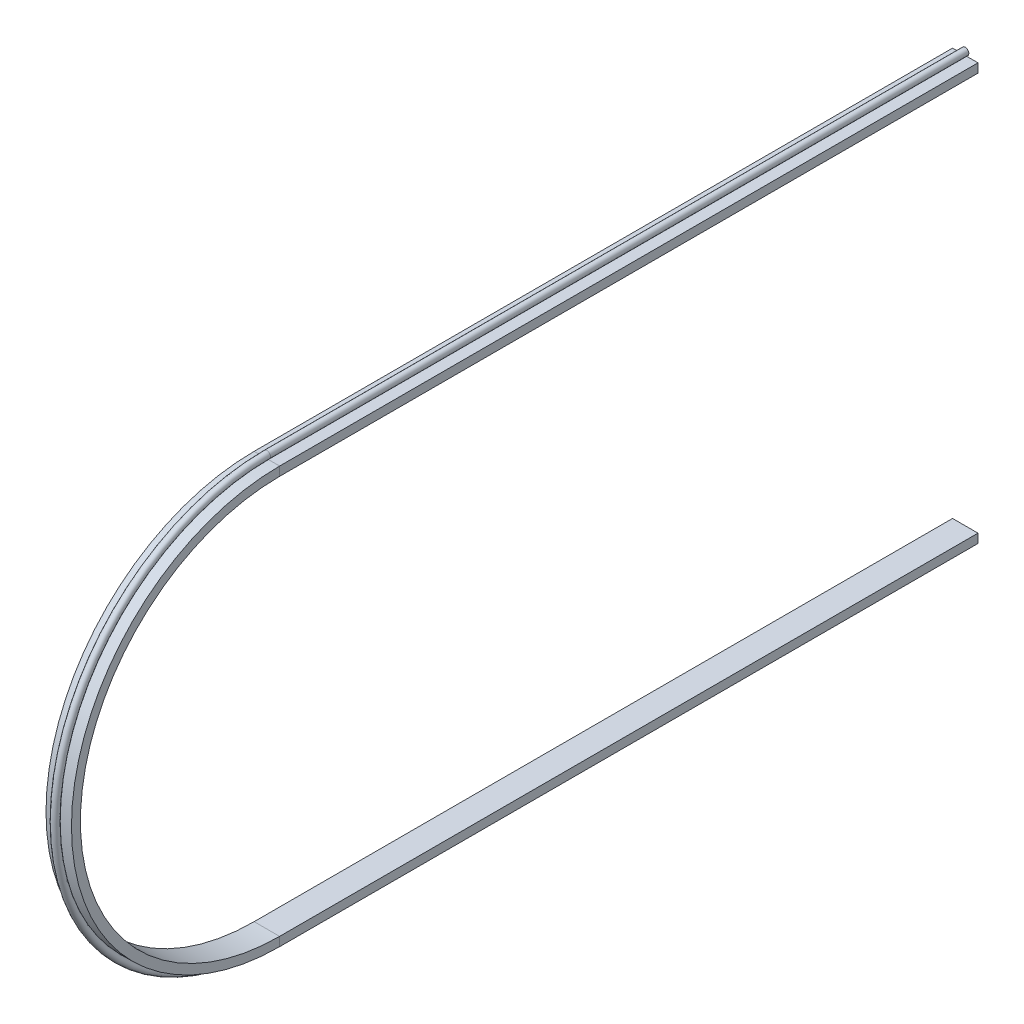
SolidWorks part; units mm, degrees
ref_plane "Front Plane" through (0, 0, 0) normal (0, 0, 1) x (1, 0, 0)
ref_plane "Top Plane" through (0, 0, 0) normal (0, 1, 0) x (1, 0, 0)
ref_plane "Right Plane" through (0, 0, 0) normal (1, 0, 0) x (0, 0, -1)
sketch "Sketch1" plane through (0, 0, 0) normal (0, 0, 1) x (1, 0, 0)
  line L1 (-6.25, -2.2) -> (6.25, -2.2)
  line L2 (-6.25, -2.2) -> (-6.25, 2.2)
  line L3 (-6.25, 2.2) -> (6.25, 2.2)
  line L4 (6.25, -2.2) -> (6.25, 2.2)
  line L5 (-6.25, -2.2) -> (6.25, 2.2) construction
  line L6 (-6.25, 2.2) -> (6.25, -2.2) construction
  point P0 (0, 0)
  dimension "D1" = 4.4
  dimension "D2" = 12.5
sketch "Sketch2" plane through (0, 0, 0) normal (0, 0, 1) x (1, 0, 0)
  line L1 (-6.25, -2.2) -> (6.25, -2.2) construction
  circle A0 centre (0, -3.95) radius 1.75
  dimension "D1" = 3.5
sketch "Sketch3" plane through (0, 0, 0) normal (1, 0, 0) x (0, 0, -1)
  line L0 (0, 0) -> (-342.9204, 0)
  line L1 (-342.9204, 200) -> (0, 200)
  arc A0 (-342.9204, 0) -> (-342.9204, 200) centre (-342.9204, 100) cw
  dimension "D2" = 100
  dimension "D1" = 342.9204
sweep "Sweep1" add profiles "Sketch1" path "Sketch3"
sweep "Sweep2" add profiles "Sketch2" path "Sketch3<2>"
sketch "Sketch3<2>" plane through (0, 0, 0) normal (1, 0, 0) x (0, 0, -1) same geometry as "Sketch3"
equation "\"length\"= 1000mm"
equation "\"bend_rad\"= 100mm"
equation "\"straight_len\"= ( \"length\" - ( pi * \"bend_rad\" ) ) / 2"
equation "\"D1@Sketch3\"=\"straight_len\""
equation "\"D2@Sketch3\"=\"bend_rad\""
